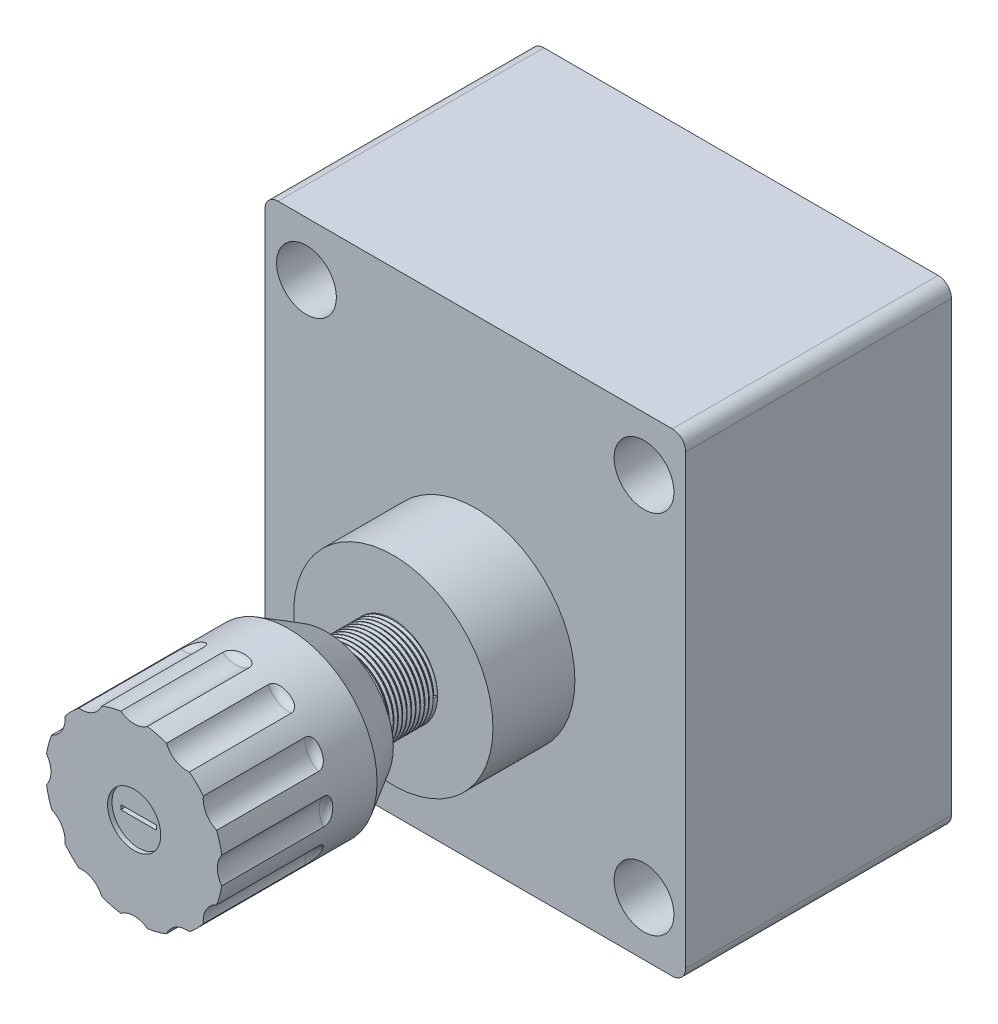
SolidWorks part; units mm, degrees
ref_plane "前视基准面" through (0, 0, 0) normal (0, 0, 1) x (1, 0, 0)
ref_plane "上视基准面" through (0, 0, 0) normal (0, 1, 0) x (1, 0, 0)
ref_plane "右视基准面" through (0, 0, 0) normal (1, 0, 0) x (0, 0, -1)
sketch "草图1" plane through (0, 0, 0) normal (0, 0, 1) x (1, 0, 0)
  line L1 (-47.5, 53.5) -> (47.5, 53.5)
  line L2 (-47.5, 53.5) -> (-47.5, -53.5)
  line L3 (-47.5, -53.5) -> (47.5, -53.5)
  line L4 (47.5, 53.5) -> (47.5, -53.5)
  line L5 (-47.5, 53.5) -> (47.5, -53.5) construction
  line L6 (-47.5, -53.5) -> (47.5, 53.5) construction
  line L7 (-38.1, 41.3) -> (38.1, 41.3) construction
  line L8 (-38.1, 41.3) -> (-38.1, -41.3) construction
  line L9 (-38.1, -41.3) -> (38.1, -41.3) construction
  line L10 (38.1, 41.3) -> (38.1, -41.3) construction
  line L11 (-38.1, 41.3) -> (38.1, -41.3) construction
  line L12 (-38.1, -41.3) -> (38.1, 41.3) construction
  circle A0 centre (-38.1, 41.3) radius 4
  circle A1 centre (38.1, 41.3) radius 4
  circle A2 centre (38.1, -41.3) radius 4
  circle A3 centre (-38.1, -41.3) radius 4
  circle A4 centre (15.9, 30.2) radius 6
  circle A5 centre (-28.6, -11.1) radius 6
  circle A6 centre (41.3, 17.5) radius 3.75
  point P0 (0, 0)
  point P6 (0, 0)
  dimension "D3" = 8
  dimension "D10" = 12
  dimension "D13" = 7.5
  dimension "D1" = 95
  dimension "D2" = 107
  dimension "D4" = 76.2
  dimension "D5" = 82.6
  dimension "D6" = 11.1
  dimension "D7" = 54
  dimension "D8" = 52.4
  dimension "D9" = 9.5
  dimension "D11" = 23.8
  dimension "D12" = 79.4
extrude "凸台-拉伸1" add sketch "草图1" against normal blind 60
sketch "草图2" plane through (0, 0, 0) normal (0, 0, 1) x (1, 0, 0)
  circle A0 centre (-38.1, 41.3) radius 6.75
  circle A1 centre (-38.1, -41.3) radius 6.75
  circle A2 centre (38.1, -41.3) radius 6.75
  circle A3 centre (38.1, 41.3) radius 6.75
  dimension "D1" = 13.5
extrude "切除-拉伸1" cut sketch "草图2" against normal blind 10
sketch "草图3" plane through (0, 0, 0) normal (0, 0, 1) x (1, 0, 0)
  circle A0 centre (15.9, 30.2) radius 6 construction
  circle A1 centre (15.9, 30.2) radius 6
  circle A2 centre (41.3, 17.5) radius 3.75 construction
  circle A3 centre (41.3, 17.5) radius 3.75
  circle A4 centre (-28.6, -11.1) radius 6 construction
  circle A5 centre (-28.6, -11.1) radius 6
extrude "凸台-拉伸2" add sketch "草图3" against normal blind 20
sketch "草图5" plane through (0, 0, 0) normal (1, 0, 0) x (0, 0, -1)
  line L0 (-36.7448, 0) -> (74.691, 0) construction
  line L1 (0, 66.5114) -> (0, -66.3947) construction
  line L2 (-85.2062, -6.7) -> (80.642, -6.7) construction
  line L3 (60, -53.5) -> (0, -53.5) construction
  line L4 (0, -29.2) -> (-18.5, -29.2)
  line L5 (-18.5, -29.2) -> (-18.5, -16.7)
  line L6 (-18.5, -16.7) -> (-33.5, -16.7)
  line L7 (-33.5, -16.7) -> (-33.5, -21.7)
  line L8 (-42.1603, -26.7) -> (-77, -26.7)
  line L9 (-77, -26.7) -> (-77, -6.7)
  line L10 (60, -53.5) -> (60, 53.5) construction
  line L11 (0, -29.2) -> (0, -6.7)
  line L12 (0, -6.7) -> (-77, -6.7)
  line L13 (-33.5, -21.7) -> (-42.1603, -26.7)
  dimension "D1" = 46.8
  dimension "D2" = 22.5
  dimension "D3" = 20
  dimension "D4" = 137
  dimension "D5" = 18.5
  dimension "D6" = 15
  dimension "D7" = 15
  dimension "D8" = 10
  dimension "D9" = 30
revolve "旋转1" add sketch "草图5" angle 360 about L2
fillet "圆角1" radius 3 4 edges at (-47.5, -53.5, -30) (47.5, -53.5, -30) (-47.5, 53.5, -30) (47.5, 53.5, -30)
sketch "草图7" plane through (0, 0, 77) normal (0, 0, 1) x (1, 0, 0)
  circle A0 centre (0, -6.7) radius 6
  dimension "D1" = 12
extrude "切除-拉伸2" cut sketch "草图7" against normal blind 1
sketch "草图8" plane through (0, 0, 76) normal (0, 0, 1) x (1, 0, 0)
  line L0 (-6, -6.7) -> (6, -6.7) construction
  line L2 (-4, -6.2) -> (4, -6.2)
  line L3 (-4, -6.2) -> (-4, -7.2)
  line L4 (-4, -7.2) -> (4, -7.2)
  line L5 (4, -6.2) -> (4, -7.2)
  line L6 (-4, -6.2) -> (4, -7.2) construction
  line L7 (-4, -7.2) -> (4, -6.2) construction
  circle A0 centre (0, -6.7) radius 6 construction
  point P5 (0, -6.7)
  dimension "D1" = 1
  dimension "D2" = 8
extrude "切除-拉伸3" cut sketch "草图8" against normal blind 2
thread "螺纹线1" pitch 1 method cut profile "螺纹线轮廓1" start angle 0, offset 0, length 15, pitch 1, diameter 20
ref_plane "基准面1" through (10, -6.7, 18.5) normal (0, -1, 0) x (1, 0, 0)
sketch "螺纹线轮廓1" plane through (10, -6.7, 18.5) normal (0, -1, 0) x (1, 0, 0)
  line L0 (0, 0) -> (0, 1) construction
  line L11 (0, 0) -> (0, 0.875)
  line L12 (0, 0.875) -> (-0.5413, 0.5625)
  line L13 (-0.5413, 0.5625) -> (-0.5413, 0.3125)
  line L15 (-0.5413, 0.3125) -> (0, 0)
  line L17 (-0.5413, 0.4375) -> (0, 0.4375) construction
  point P2 (0, 0)
  dimension "Pitch" = 1
  dimension "Profile_Angle" = 60
  dimension "Profile_Land" = 0.25
  dimension "Profile_Height" = 0.5413
sketch "草图9" plane through (0, 0, 77) normal (0, 0, 1) x (1, 0, 0)
  line L0 (0, 19.1882) -> (0, -34.8382) construction
  line L1 (-34.3619, -6.7) -> (33.3412, -6.7) construction
  arc A0 (-3, 13.0737) -> (3, 13.0737) centre (0, 17.0737) ccw
  circle A1 centre (0, -6.7) radius 20 construction
  arc A2 (-20, -6.7) -> (20, -6.7) centre (0, -6.7) ccw
  arc A3 (3, 13.0737) -> (-3, 13.0737) centre (0, -6.7) ccw
  circle M2 centre (0, -6.7) radius 20
  dimension "D2" = 5
  dimension "D1" = 6
extrude "切除-拉伸4" cut sketch "草图9" against normal blind 25 contours A0 M2 region at (0, 12.7598, 77)
fillet "圆角2" radius 2 1 edges at (0, 12.0737, 52)
pattern_circular "阵列(圆周)1" count 12 over 360 about axis through (0, -6.7, 42.1603) along (0, 0, 1) of "切除-拉伸4", "圆角2"
